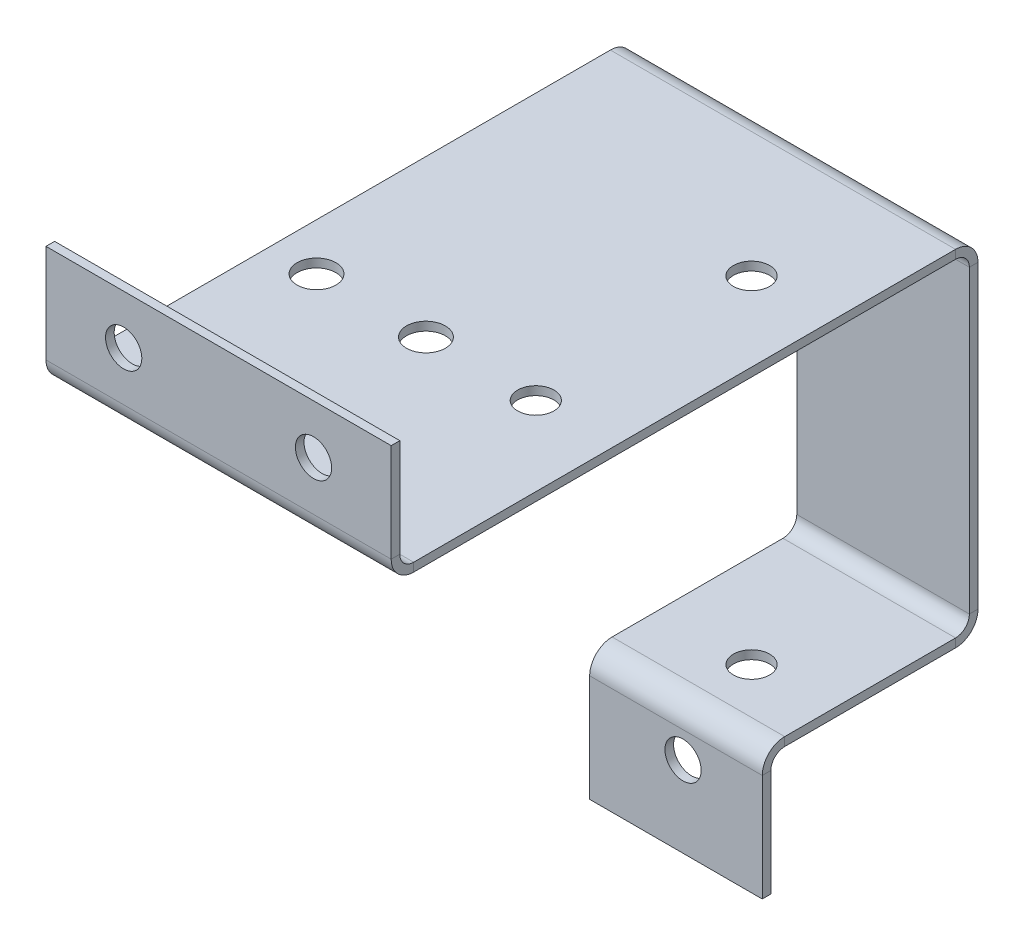
SolidWorks part; units mm, degrees
note: The reader was unsure of these and kept them because the rebuilt part matched: flange length of "Edge-Flange1", "Edge-Flange2", "Edge-Flange3", "Edge-Flange4".
material "Plain Carbon Steel"
ref_plane "Front Plane" through (0, 0, 0) normal (0, 0, 1) x (1, 0, 0)
ref_plane "Top Plane" through (0, 0, 0) normal (0, 1, 0) x (1, 0, 0)
ref_plane "Right Plane" through (0, 0, 0) normal (1, 0, 0) x (0, 0, -1)
sketch "Sketch1" plane through (0, 0, 0) normal (0, 0, 1) x (1, 0, 0)
  line L0 (0, 0) -> (0, 3)
  line L1 (0, 3) -> (-40, 3)
  line L5 (-20, -37) -> (-18.1651, -37)
  line L6 (0, 0) -> (0, -37)
  line L7 (0, -37) -> (-18.1651, -37)
  line L8 (-40, 3) -> (-40, 0)
  line L9 (-40, 0) -> (-20, 0)
  line L10 (-20, 0) -> (-20, -37)
  dimension "D1" = 3
  dimension "D2" = 40
  dimension "D3" = 40
base flange "Base-Flange1" sketch "Sketch1" thickness 1 reverse thickness direction no parameters "D1"=1.6
edge flange "Edge-Flange1" sketch "Sketch8" flange angle 90 flange length 68 flange position material inside bend radius 1.6 thickness 1 relief rectangular parameters "D6"=10
sketch "Sketch8" plane through (0, 3, 0) normal (0, 1, 0) x (-1, 0, 0)
  line L0 (0, 0) -> (40, 0) construction
  line L1 (0, 0) -> (40, 0)
  line L2 (0, 0) -> (0, 67)
  line L3 (0, 67) -> (40, 67)
  line L4 (40, 67) -> (40, 0)
bend "EdgeBend1" bend radius 1.6 bend angle 90 parameters "D5"=1
edge flange "Edge-Flange2" sketch "Sketch11" flange angle 90 flange length 14 flange position material inside bend radius 1.6 thickness 1 relief rectangular parameters "D6"=10
sketch "Sketch11" plane through (0, 3, 67) normal (0, 0, 1) x (1, 0, 0)
  line L0 (-40, 0) -> (0, 0) construction
  line L1 (-40, 0) -> (0, 0)
  line L2 (-40, 0) -> (-40, 13)
  line L3 (-40, 13) -> (0, 13)
  line L4 (0, 13) -> (0, 0)
bend "EdgeBend2" bend radius 1.6 bend angle 90 parameters "D5"=2
edge flange "Edge-Flange3" sketch "Sketch14" flange angle 90 flange length 25 flange position material inside bend radius 1.6 thickness 1 relief rectangular parameters "D6"=10
sketch "Sketch14" plane through (0, -37, 0) normal (0, -1, 0) x (1, 0, 0)
  line L0 (-20, 0) -> (0, 0) construction
  line L1 (-20, 0) -> (0, 0)
  line L2 (-20, 0) -> (-20, 24)
  line L3 (-20, 24) -> (0, 24)
  line L4 (0, 24) -> (0, 0)
bend "EdgeBend3" bend radius 1.6 bend angle 90 parameters "D5"=3
edge flange "Edge-Flange4" sketch "Sketch17" flange angle 90 flange length 15 flange position material inside bend radius 1.6 thickness 1 relief rectangular parameters "D6"=10
sketch "Sketch17" plane through (0, -37, 24) normal (0, 0, 1) x (-1, 0, 0)
  line L2 (0, 0) -> (0, 14)
  line L3 (0, 14) -> (20, 14)
  line L4 (20, 14) -> (20, 0)
  line L7 (0, 0) -> (20, 0) construction
  line L8 (0, 0) -> (20, 0)
bend "EdgeBend4" bend radius 1.6 bend angle 90 parameters "D5"=4
sketch "Sketch18" plane through (0, 0, 66) normal (0, 0, -1) x (-1, 0, 0)
  line L0 (0, 10.3) -> (9, 10.3)
  line L2 (0, 4.6) -> (0, 16) construction
  line L3 (40, 10.3) -> (31, 10.3)
  line L4 (40, 16) -> (40, 4.6) construction
  circle A0 centre (9, 10.3) radius 2.1
  circle A1 centre (31, 10.3) radius 2.1
  dimension "D3" = 4.2
  dimension "D4" = 4.2
  dimension "D1" = 9
  dimension "D2" = 9
extrude "Cut-Extrude1" cut sketch "Sketch18" against normal blind 6
sketch "Sketch19" plane through (0, 0, 23) normal (0, 0, -1) x (-1, 0, 0)
  circle A0 centre (9.1783, -41.6379) radius 2.1
  dimension "D1" = 4.2
extrude "Cut-Extrude2" cut sketch "Sketch19" against normal blind 6 normal cut yes
sketch "Sketch20" plane through (0, 3, 0) normal (0, 1, 0) x (1, 0, 0)
  circle A0 centre (-9.1533, -41.0902) radius 2.1
  circle A1 centre (-9.1533, -16.0902) radius 2.1
  dimension "D1" = 4.2
  dimension "D2" = 4.2
extrude "Cut-Extrude3" cut sketch "Sketch20" against normal blind 50 normal cut yes
sketch "Sketch21" plane through (0, 2, 0) normal (0, -1, 0) x (1, 0, 0)
  line L0 (-9.1533, 41.0902) -> (-21.8833, 41.0902)
  line L1 (-21.8833, 41.0902) -> (-34.5633, 41.0902)
  circle A1 centre (-21.8833, 41.0902) radius 2.25
  circle A2 centre (-34.5633, 41.0902) radius 2.25
  dimension "D1" = 12.73
  dimension "D2" = 4.5
  dimension "D4" = 4.5
  dimension "D3" = 12.68
extrude "Cut-Extrude4" cut sketch "Sketch21" against normal blind 50
sketch "Bend-Lines1" [suppressed] plane through (0, 0, 0) normal (0, 1, 0) x (1, 0, 0)
sketch "Bounding-Box1" [suppressed] plane through (0, 0, 0) normal (0, 1, 0) x (1, 0, 0)
sheet metal parameters "Sheet-Metal8" thickness 1 parameters "D1"=1.6
flat pattern "Flat-Pattern8" [suppressed]
sketch "Bend-Lines2" plane through (0, 0, 0) normal (0, 1, 0) x (1, 0, 0)
sketch3d "Bounding-Box2" [suppressed]
  line L0 (0, 3, 0) -> (0, -52, 0) construction
  line L1 (40, 3, 0) -> (40, -52, 0) construction
  line L2 (0, 3, 0) -> (40, 3, 0) construction
  line L3 (0, -52, 0) -> (40, -52, 0) construction
sheet metal parameters "Sheet-Metal9" thickness 1 parameters "D1"=1.6
flat pattern "Flat-Pattern8"
sketch "Bend-Lines2" plane through (0, 0, 0) normal (0, 0, 1) x (1, 0, 0)
  line L0 (0, 2.0493) -> (-40, 2.0493) construction
  line L1 (0, 2.0493) -> (-40, 2.0493) construction
sketch3d "Bounding-Box2" [suppressed]
  line L0 (0, 65.0987, 0) -> (0, -52, 0) construction
  line L1 (-40, 65.0987, 0) -> (-40, -52, 0) construction
  line L2 (0, 65.0987, 0) -> (-40, 65.0987, 0) construction
  line L3 (0, -52, 0) -> (-40, -52, 0) construction
bend of the flat pattern "Flatten-<EdgeBend1>1"
sheet metal parameters "Sheet-Metal10" thickness 1 parameters "D1"=1.6
flat pattern "Flat-Pattern8"
sketch "Bend-Lines2" plane through (0, 0, 0) normal (0, 0, 1) x (1, 0, 0)
  line L0 (0, 2.0493) -> (-40, 2.0493) construction
  line L1 (0, 2.0493) -> (-40, 2.0493) construction
  line L2 (0, 68.148) -> (-40, 68.148) construction
  line L3 (0, 68.148) -> (-40, 68.148) construction
sketch3d "Bounding-Box2" [suppressed]
  line L0 (0, 81.1973, 0) -> (0, -37, 0) construction
  line L1 (-40, 81.1973, 0) -> (-40, -37, 0) construction
  line L2 (0, 81.1973, 0) -> (-40, 81.1973, 0) construction
  line L3 (0, -37, 0) -> (-40, -37, 0) construction
bend of the flat pattern "Flatten-<EdgeBend1>1"
bend of the flat pattern "Flatten-<EdgeBend2>1"
sheet metal parameters "Sheet-Metal11" thickness 1 parameters "D1"=1.6
flat pattern "Flat-Pattern8"
sketch "Bend-Lines2" plane through (0, 0, 0) normal (0, 0, 1) x (1, 0, 0)
  line L0 (0, 2.0493) -> (-40, 2.0493) construction
  line L1 (0, 2.0493) -> (-40, 2.0493) construction
  line L2 (0, 68.148) -> (-40, 68.148) construction
  line L3 (0, 68.148) -> (-40, 68.148) construction
  line L4 (-20, -36.0493) -> (0, -36.0493) construction
  line L5 (-20, -36.0493) -> (0, -36.0493) construction
sketch3d "Bounding-Box2" [suppressed]
  line L0 (0, 81.1973, 0) -> (0, -58.0987, 0) construction
  line L1 (-40, 81.1973, 0) -> (-40, -58.0987, 0) construction
  line L2 (0, 81.1973, 0) -> (-40, 81.1973, 0) construction
  line L3 (0, -58.0987, 0) -> (-40, -58.0987, 0) construction
bend of the flat pattern "Flatten-<EdgeBend1>1"
bend of the flat pattern "Flatten-<EdgeBend2>1"
bend of the flat pattern "Flatten-<EdgeBend3>1"
sheet metal parameters "Sheet-Metal12" thickness 1 parameters "D1"=1.6
flat pattern "Flat-Pattern8"
sketch "Bend-Lines2" plane through (0, 0, 0) normal (0, 0, 1) x (1, 0, 0)
  line L0 (0, 2.0493) -> (-40, 2.0493) construction
  line L1 (0, 2.0493) -> (-40, 2.0493) construction
  line L2 (0, 68.148) -> (-40, 68.148) construction
  line L3 (0, 68.148) -> (-40, 68.148) construction
  line L4 (-20, -36.0493) -> (0, -36.0493) construction
  line L5 (-20, -36.0493) -> (0, -36.0493) construction
  line L6 (-20, -59.148) -> (0, -59.148) construction
  line L7 (-20, -59.148) -> (0, -59.148) construction
sketch3d "Bounding-Box2" [suppressed]
  line L0 (0, 81.1973, 0) -> (0, -73.1973, 0) construction
  line L1 (-40, 81.1973, 0) -> (-40, -73.1973, 0) construction
  line L2 (0, 81.1973, 0) -> (-40, 81.1973, 0) construction
  line L3 (0, -73.1973, 0) -> (-40, -73.1973, 0) construction
bend of the flat pattern "Flatten-<EdgeBend1>1"
bend of the flat pattern "Flatten-<EdgeBend2>1"
bend of the flat pattern "Flatten-<EdgeBend3>1"
bend of the flat pattern "Flatten-<EdgeBend4>1"
sheet metal parameters "Sheet-Metal13" thickness 1 parameters "D1"=1.6
flat pattern "Flat-Pattern8"
sketch "Bend-Lines2" plane through (0, 0, 0) normal (0, 0, 1) x (1, 0, 0)
  line L0 (0, 2.0493) -> (-40, 2.0493) construction
  line L1 (0, 2.0493) -> (-40, 2.0493) construction
  line L2 (0, 68.148) -> (-40, 68.148) construction
  line L3 (0, 68.148) -> (-40, 68.148) construction
  line L4 (-20, -36.0493) -> (0, -36.0493) construction
  line L5 (-20, -36.0493) -> (0, -36.0493) construction
  line L6 (-20, -59.148) -> (0, -59.148) construction
  line L7 (-20, -59.148) -> (0, -59.148) construction
sketch3d "Bounding-Box2" [suppressed]
  line L0 (0, 81.1973, 0) -> (0, -73.1973, 0) construction
  line L1 (-40, 81.1973, 0) -> (-40, -73.1973, 0) construction
  line L2 (0, 81.1973, 0) -> (-40, 81.1973, 0) construction
  line L3 (0, -73.1973, 0) -> (-40, -73.1973, 0) construction
bend of the flat pattern "Flatten-<EdgeBend1>1"
bend of the flat pattern "Flatten-<EdgeBend2>1"
bend of the flat pattern "Flatten-<EdgeBend3>1"
bend of the flat pattern "Flatten-<EdgeBend4>1"
sheet metal parameters "Sheet-Metal14" thickness 1 parameters "D1"=1.6
flat pattern "Flat-Pattern8"
sketch "Bend-Lines2" plane through (0, 0, 0) normal (0, 0, 1) x (1, 0, 0)
  line L0 (0, 2.0493) -> (-40, 2.0493) construction
  line L1 (0, 2.0493) -> (-40, 2.0493) construction
  line L2 (0, 68.148) -> (-40, 68.148) construction
  line L3 (0, 68.148) -> (-40, 68.148) construction
  line L4 (-20, -36.0493) -> (0, -36.0493) construction
  line L5 (-20, -36.0493) -> (0, -36.0493) construction
  line L6 (-20, -59.148) -> (0, -59.148) construction
  line L7 (-20, -59.148) -> (0, -59.148) construction
sketch3d "Bounding-Box2" [suppressed]
  line L0 (0, 81.1973, 0) -> (0, -73.1973, 0) construction
  line L1 (-40, 81.1973, 0) -> (-40, -73.1973, 0) construction
  line L2 (0, 81.1973, 0) -> (-40, 81.1973, 0) construction
  line L3 (0, -73.1973, 0) -> (-40, -73.1973, 0) construction
bend of the flat pattern "Flatten-<EdgeBend1>1"
bend of the flat pattern "Flatten-<EdgeBend2>1"
bend of the flat pattern "Flatten-<EdgeBend3>1"
bend of the flat pattern "Flatten-<EdgeBend4>1"
sheet metal parameters "Sheet-Metal15" thickness 1 parameters "D1"=1.6
flat pattern "Flat-Pattern8"
sketch "Bend-Lines2" plane through (0, 0, 0) normal (0, 0, 1) x (1, 0, 0)
  line L0 (0, 2.0493) -> (-40, 2.0493) construction
  line L1 (0, 2.0493) -> (-40, 2.0493) construction
  line L2 (0, 68.148) -> (-40, 68.148) construction
  line L3 (0, 68.148) -> (-40, 68.148) construction
  line L4 (-20, -36.0493) -> (0, -36.0493) construction
  line L5 (-20, -36.0493) -> (0, -36.0493) construction
  line L6 (-20, -59.148) -> (0, -59.148) construction
  line L7 (-20, -59.148) -> (0, -59.148) construction
sketch3d "Bounding-Box2" [suppressed]
  line L0 (0, 81.1973, 0) -> (0, -73.1973, 0) construction
  line L1 (-40, 81.1973, 0) -> (-40, -73.1973, 0) construction
  line L2 (0, 81.1973, 0) -> (-40, 81.1973, 0) construction
  line L3 (0, -73.1973, 0) -> (-40, -73.1973, 0) construction
bend of the flat pattern "Flatten-<EdgeBend1>1"
bend of the flat pattern "Flatten-<EdgeBend2>1"
bend of the flat pattern "Flatten-<EdgeBend3>1"
bend of the flat pattern "Flatten-<EdgeBend4>1"
sheet metal parameters "Sheet-Metal16" thickness 1 parameters "D1"=1.6
flat pattern "Flat-Pattern8"
sketch "Bend-Lines2" plane through (0, 0, 0) normal (0, 0, 1) x (1, 0, 0)
  line L0 (0, 2.0493) -> (-40, 2.0493) construction
  line L1 (0, 2.0493) -> (-40, 2.0493) construction
  line L2 (0, 68.148) -> (-40, 68.148) construction
  line L3 (0, 68.148) -> (-40, 68.148) construction
  line L4 (-20, -36.0493) -> (0, -36.0493) construction
  line L5 (-20, -36.0493) -> (0, -36.0493) construction
  line L6 (-20, -59.148) -> (0, -59.148) construction
  line L7 (-20, -59.148) -> (0, -59.148) construction
sketch3d "Bounding-Box2" [suppressed]
  line L0 (0, 81.1973, 0) -> (0, -73.1973, 0) construction
  line L1 (-40, 81.1973, 0) -> (-40, -73.1973, 0) construction
  line L2 (0, 81.1973, 0) -> (-40, 81.1973, 0) construction
  line L3 (0, -73.1973, 0) -> (-40, -73.1973, 0) construction
bend of the flat pattern "Flatten-<EdgeBend1>1"
bend of the flat pattern "Flatten-<EdgeBend2>1"
bend of the flat pattern "Flatten-<EdgeBend3>1"
bend of the flat pattern "Flatten-<EdgeBend4>1"
